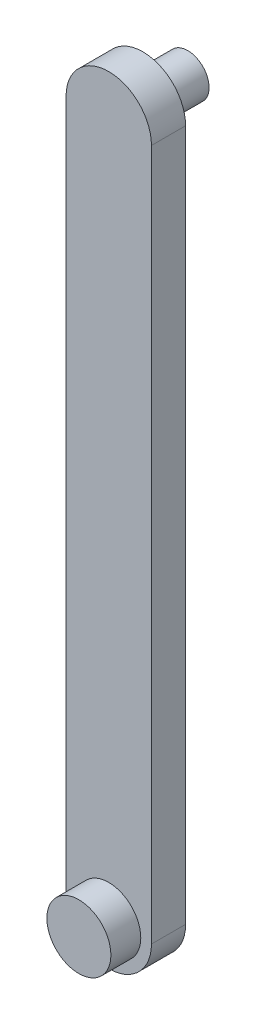
SolidWorks part; units mm, degrees
material "Gray Cast Iron"
ref_plane "Front Plane" through (0, 0, 0) normal (0, 0, 1) x (1, 0, 0)
ref_plane "Top Plane" through (0, 0, 0) normal (0, 1, 0) x (1, 0, 0)
ref_plane "Right Plane" through (0, 0, 0) normal (1, 0, 0) x (0, 0, -1)
sketch "Sketch1" plane through (0, 0, 0) normal (0, 0, 1) x (1, 0, 0)
  line L0 (0, 0) -> (0, 1620) construction
  line L1 (-100, 0) -> (-100, 1620)
  line L2 (100, 0) -> (100, 1620)
  arc A0 (-100, 0) -> (100, 0) centre (0, 0) ccw
  arc A1 (100, 1620) -> (-100, 1620) centre (0, 1620) ccw
  circle A2 centre (0, 1620) radius 50
  circle A3 centre (0, 0) radius 75
  point P3 (0, 810)
  dimension "D1" = 200
  dimension "D3" = 150
  dimension "D4" = 100
  dimension "D2" = 1620
extrude "Boss-Extrude1" add sketch "Sketch1" along normal blind 80
extrude "Boss-Extrude2" add sketch "Sketch1<2>" along normal blind 150 separate body contours A3 region at (0, 0, 0)
sketch "Sketch1<2>" plane through (0, 0, 0) normal (0, 0, 1) x (1, 0, 0) same geometry as "Sketch1"
extrude "Boss-Extrude3" add sketch "Sketch1<4>" against normal blind 105 and the other way up to surface (80 mm away) contours A2 other way up to face at (50, 1620, 80)
sketch "Sketch1<4>" plane through (0, 0, 0) normal (0, 0, 1) x (1, 0, 0) same geometry as "Sketch1"
